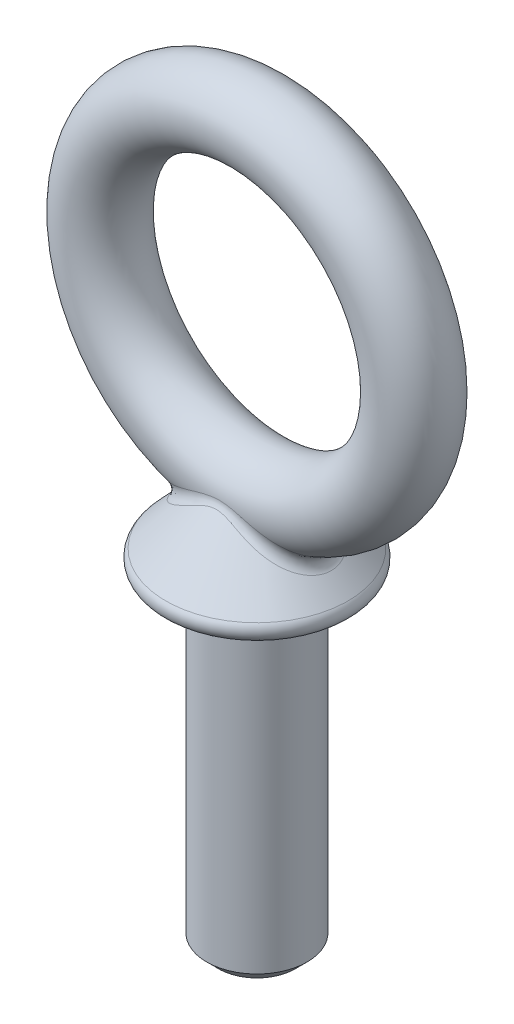
SolidWorks part; units mm, degrees
ref_plane "Front Plane" through (0, 0, 0) normal (0, 0, 1) x (1, 0, 0)
ref_plane "Top Plane" through (0, 0, 0) normal (0, 1, 0) x (1, 0, 0)
ref_plane "Right Plane" through (0, 0, 0) normal (1, 0, 0) x (0, 0, -1)
sketch "Sketch1" plane through (0, 0, 0) normal (0, 0, 1) x (1, 0, 0)
  line L0 (0, -24.6062) -> (0, -70.6438) construction
  line L1 (-6.35, -70.6438) -> (6.35, -70.6438) construction
  line L2 (6.5615, -70.5216) -> (6.5615, -72.4755) construction
  line L3 (0, -24.6062) -> (0, -15.0812) construction
  line L4 (-11.9062, -29.3688) -> (11.9062, -29.3688) construction
  line L5 (6.5615, -72.4755) -> (4.8694, -71.4986) construction
  line L6 (4.8694, -71.4986) -> (6.5615, -70.5216) construction
  line L7 (4.8694, -71.4986) -> (5.0809, -71.4986) construction
  line L8 (6.5615, -71.4986) -> (6.35, -71.4986) construction
  line L9 (5.0809, -71.6207) -> (5.0809, -71.3764) construction
  line L10 (6.35, -72.3534) -> (6.35, -70.6438) construction
  line L11 (6.4558, -72.4144) -> (6.4558, -70.5827) construction
  circle A0 centre (0, 0) radius 24.6062 construction
  circle A1 centre (0, 19.8438) radius 4.7625 construction
  circle A2 centre (0, 0) radius 15.0813 construction
  point P7 (0, -24.6062)
  point P9 (0, -29.3688)
  point P10 (0, 24.6062)
  point P11 (0, 15.0812)
  point P14 (0, -70.6438)
  point P17 (0, 0)
  point P19 (0, -19.8438)
  point P21 (0, -29.3688)
  point P32 (5.0809, -71.4986)
  point P35 (6.35, -71.4986)
  point P38 (6.4558, -71.4986)
  dimension "Pitch" = 1.9538
  dimension "D1" = 0.2442
sketch "Sketch2" plane through (0, 0, 0) normal (0, 1, 0) x (1, 0, 0)
  circle A0 centre (0, 0) radius 6.35
extrude "Boss-Extrude1" add sketch "Sketch2" against normal up to vertex (70.6437 mm away) from vertex up to point (0, -70.6438, 0) starting at point (0, -29.3688, 0)
sketch "Sketch3" plane through (0, -70.6438, 0) normal (0, -1, 0) x (1, 0, 0)
  circle A1 centre (0, 0) radius 6.35
  circle A2 centre (0, 0) radius 6.35
  point P0 (6.35, 0)
  point P1 (0, -6.35)
  dimension "D1" = 0
sketch "Sketch4" plane through (0, 0, 0) normal (0, 0, 1) x (1, 0, 0)
  line L0 (5.0809, -71.3764) -> (5.0809, -71.6207)
  line L1 (5.0809, -71.6207) -> (6.4558, -72.4144)
  line L2 (6.4558, -72.4144) -> (6.4558, -70.5827)
  line L3 (6.4558, -70.5827) -> (5.0809, -71.3764)
sketch "Sketch5" plane through (0, -70.6438, 0) normal (0, -1, 0) x (1, 0, 0)
  circle A0 centre (0, 0) radius 4.8694
extrude "Cut-Extrude1" cut sketch "Sketch5" against normal through all draft 45 flip side to cut
sketch "Sketch6" plane through (0, 0, 0) normal (1, 0, 0) x (0, 0, -1)
  circle A0 centre (0, 19.8438) radius 4.7625
ref_axis "Axis1" through (0, 0, -7.6398) along (0, 0, 1)
revolve "Revolve1" add sketch "Sketch6" angle 360 about axis through (0, 0, -7.6398) along (0, 0, 1)
sketch "Sketch8" plane through (0, 0, 0) normal (0, 0, 1) x (1, 0, 0)
  line L0 (0, -29.3688) -> (0, -19.8438)
  line L1 (0, -19.8438) -> (-4.7625, -19.8438)
  line L2 (-10.5172, -29.3688) -> (-11.9062, -29.3688) construction
  line L3 (-11.9062, -29.3688) -> (-11.9062, -27.9797) construction
  line L4 (0, -29.3688) -> (11.9062, -29.3688) construction
  line L5 (-11.9062, -29.3688) -> (11.9062, -29.3688) construction
  line L6 (-11.5284, -27.0273) -> (-4.7625, -19.8438)
  line L7 (-11.9062, -29.3688) -> (0, -29.3688) construction
  line L9 (-10.5172, -29.3688) -> (0, -29.3688)
  arc A0 (-11.5284, -27.0273) -> (-10.5172, -29.3688) centre (-10.5172, -27.9797) ccw
  circle A1 centre (0, -19.8438) radius 4.7625 construction
  dimension "D1" = 1.3891
revolve "Revolve2" add sketch "Sketch8" angle 360 about L0
fillet "Fillet1" radius 1.3891 1 edges at (7.3014, -22.9015, 2.2575)
sketch "SketchX" plane through (0, 0, 0) normal (1, 0, 0) x (0, 0, -1)
  line L0 (6.35, -70.6438) -> (6.35, -65.7591) construction
  line L1 (0, -70.6438) -> (6.35, -70.6438) construction
  dimension "D1" = 4.8846
  dimension "D2" = 6.35
ref_axis "Center Axis 1" through (0, 21.5506, 0) along (0, -1, 0)
ref_axis "Center Axis 2" through (0, 0, -7.6398) along (0, 0, 1)
equation "\"D1@Sketch1\"=\"Pitch@Sketch1\"/8"
equation "\"Pitch\" = \"Pitch@Sketch1\""
equation "\"D2@SketchX\" = \"Thread OD@Sketch1\" / 2"
